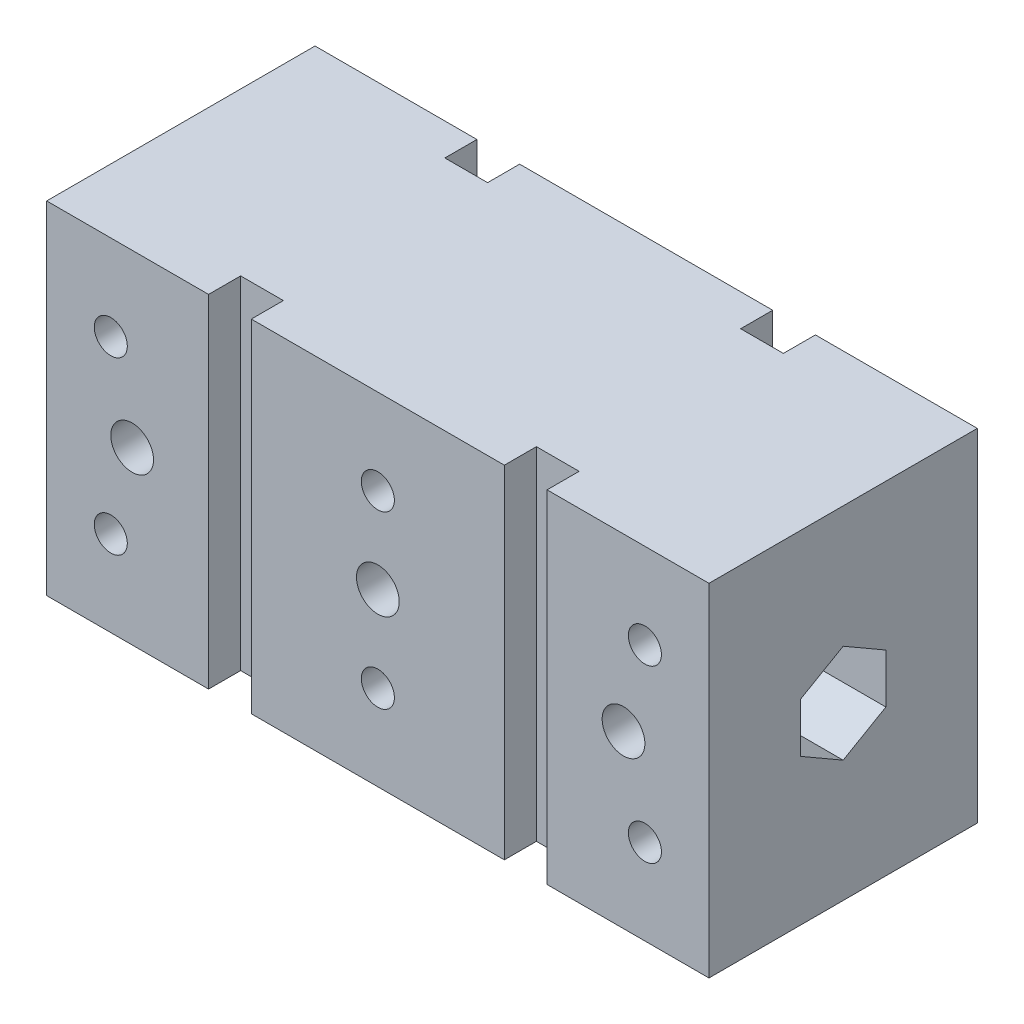
SolidWorks part; units mm, degrees
material "PET"
ref_plane "Front" through (0, 0, 0) normal (0, 0, 1) x (1, 0, 0)
ref_plane "Top" through (0, 0, 0) normal (0, 1, 0) x (1, 0, 0)
ref_plane "Right" through (0, 0, 0) normal (1, 0, 0) x (0, 0, -1)
sketch "Sketch1" plane through (0, 0, 0) normal (1, 0, 0) x (0, 0, -1)
  line L1 (19.939, -25.4) -> (-19.939, -25.4)
  line L2 (19.939, -25.4) -> (19.939, 25.4)
  line L3 (19.939, 25.4) -> (-19.939, 25.4)
  line L4 (-19.939, -25.4) -> (-19.939, 25.4)
  line L5 (19.939, -25.4) -> (-19.939, 25.4) construction
  line L6 (19.939, 25.4) -> (-19.939, -25.4) construction
  point P0 (0, 0)
  dimension "D1" = 50.8
  dimension "D2" = 39.878
extrude "Boss-Extrude1" add sketch "Sketch1" along normal blind 98.425
sketch "Sketch3" plane through (98.425, 0, 0) normal (1, 0, 0) x (0, 0, -1)
  line L1 (6.35, 3.6662) -> (0, 7.3323)
  line L2 (0, 7.3323) -> (-6.35, 3.6662)
  line L3 (-6.35, 3.6662) -> (-6.35, -3.6662)
  line L4 (-6.35, -3.6662) -> (0, -7.3323)
  line L5 (0, -7.3323) -> (6.35, -3.6662)
  line L6 (6.35, -3.6662) -> (6.35, 3.6662)
  circle A0 centre (0, 0) radius 6.35 construction
  dimension "D1" = 12.7
extrude "Cut-Extrude2" cut sketch "Sketch3" against normal through all
ref_axis "Axis1" through (-80.9, 0, 0) along (1, 0, 0)
sketch "Sketch9" plane through (0, 0, 19.939) normal (0, 0, 1) x (1, 0, 0)
  line L0 (12.7, 0) -> (49.2125, 0) construction
  line L1 (49.2125, 0) -> (85.725, 0) construction
  line L2 (0, 25.4) -> (0, -25.4) construction
  line L3 (98.425, 25.4) -> (98.425, -25.4) construction
  circle A0 centre (12.7, 0) radius 3.175
  circle A1 centre (49.2125, 0) radius 3.175
  circle A2 centre (85.725, 0) radius 3.175
  point P9 (0, 0)
  dimension "D1" = 6.35
  dimension "D2" = 12.7
  dimension "D3" = 12.7
extrude "Cut-Extrude4" cut sketch "Sketch9" against normal through all
sketch "Sketch4" plane through (0, 25.4, 0) normal (0, 1, 0) x (1, 0, 0)
  line L0 (98.425, 19.939) -> (0, 19.939) construction
  line L1 (24.0589, -19.939) -> (30.4089, -19.939)
  line L2 (24.0589, -19.939) -> (24.0589, -15.1765)
  line L3 (24.0589, -15.1765) -> (30.4089, -15.1765)
  line L4 (30.4089, -19.939) -> (30.4089, -15.1765)
  line L5 (24.0589, -19.939) -> (30.4089, -15.1765) construction
  line L6 (24.0589, -15.1765) -> (30.4089, -19.939) construction
  line L7 (68.0161, -15.1765) -> (74.3661, -15.1765)
  line L8 (68.0161, -15.1765) -> (68.0161, -19.939)
  line L9 (68.0161, -19.939) -> (74.3661, -19.939)
  line L10 (74.3661, -15.1765) -> (74.3661, -19.939)
  line L11 (68.0161, -15.1765) -> (74.3661, -19.939) construction
  line L12 (68.0161, -19.939) -> (74.3661, -15.1765) construction
  line L13 (68.0161, 19.939) -> (74.3661, 19.939)
  line L14 (68.0161, 19.939) -> (68.0161, 15.1765)
  line L15 (68.0161, 15.1765) -> (74.3661, 15.1765)
  line L16 (74.3661, 19.939) -> (74.3661, 15.1765)
  line L17 (68.0161, 19.939) -> (74.3661, 15.1765) construction
  line L18 (68.0161, 15.1765) -> (74.3661, 19.939) construction
  line L19 (24.0589, 19.939) -> (30.4089, 19.939)
  line L20 (24.0589, 19.939) -> (24.0589, 15.1765)
  line L21 (24.0589, 15.1765) -> (30.4089, 15.1765)
  line L22 (30.4089, 19.939) -> (30.4089, 15.1765)
  line L23 (24.0589, 19.939) -> (30.4089, 15.1765) construction
  line L24 (24.0589, 15.1765) -> (30.4089, 19.939) construction
  line L25 (98.425, 19.939) -> (98.425, -19.939) construction
  line L26 (0, 19.939) -> (0, -19.939) construction
  line L29 (98.425, -19.939) -> (0, -19.939) construction
  point P0 (27.2339, -17.5578)
  point P5 (71.1911, -17.5578)
  point P10 (71.1911, 17.5577)
  point P15 (27.2339, 17.5577)
  dimension "D1" = 24.0589
  dimension "D2" = 6.35
  dimension "D3" = 4.7625
  dimension "D4" = 24.0589
extrude "Cut-Extrude3" cut sketch "Sketch4" against normal through all
sketch "Sketch7" plane through (0, 0, 19.939) normal (0, 0, 1) x (1, 0, 0)
  line L0 (98.425, 25.4) -> (74.3661, 25.4) construction
  line L1 (0, 25.4) -> (0, -25.4) construction
  line L2 (98.425, 25.4) -> (98.425, -25.4) construction
  line L3 (9.525, 12.7) -> (49.2125, 12.7) construction
  line L4 (49.2125, 12.7) -> (88.9, 12.7) construction
  point P0 (9.525, 12.7)
  point P2 (49.2125, 12.7)
  point P4 (88.9, 12.7)
  point P6 (88.9, -12.7)
  point P8 (49.2125, -12.7)
  point P10 (9.525, -12.7)
  dimension "D1" = 25.4
  dimension "D2" = 12.7
  dimension "D3" = 9.525
  dimension "D4" = 9.525
hole_wizard "#10 (0.1935) Diameter Hole1" positions "Sketch7" profile "Sketch6" hole size "#10" standard "ANSI Inch" end condition up to next
sketch "Sketch6" plane through (9.525, 12.7, 19.939) normal (1, 0, 0) x (0, -1, 0)
  line L0 (0, 0) -> (0, 39.878)
  line L1 (0, 39.878) -> (2.4574, 39.878)
  line L2 (2.4574, 39.878) -> (2.4574, 0)
  line L5 (2.4574, 0) -> (0, 0)
  line L11 (0, -6.35) -> (0, 107.95) construction
  dimension "Thru Hole Dia." = 4.9149
  dimension "Thru Hole Depth" = 39.878
